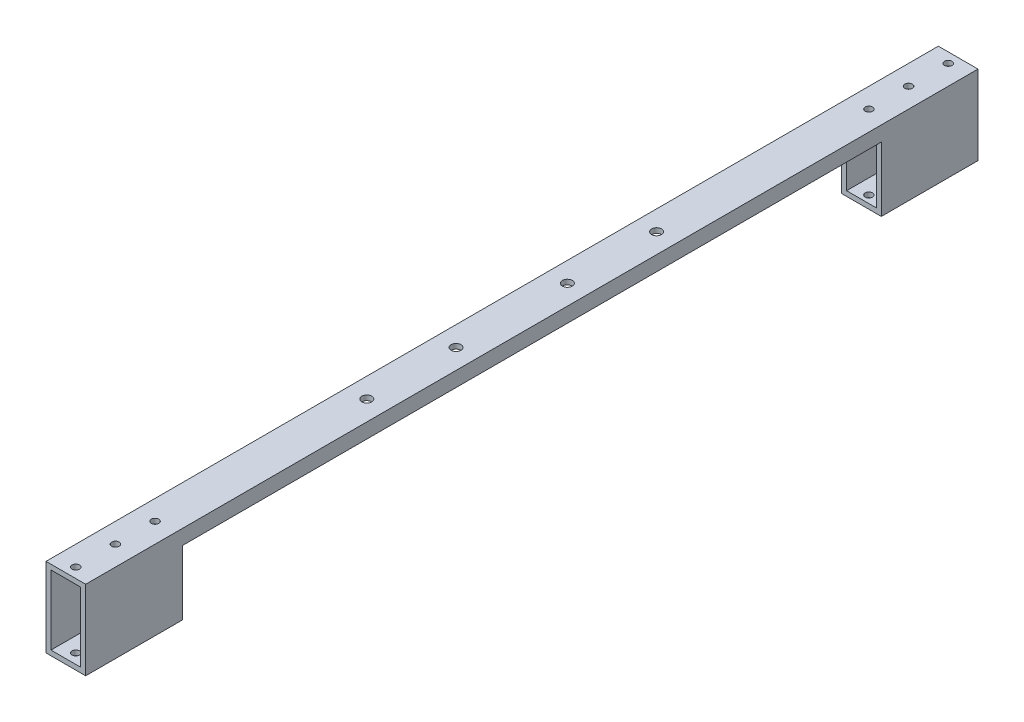
SolidWorks part; units mm, degrees
material "6061-T6 (SS)"
ref_plane "Front Plane" through (0, 0, 0) normal (0, 0, 1) x (1, 0, 0)
ref_plane "Top Plane" through (0, 0, 0) normal (0, 1, 0) x (1, 0, 0)
ref_plane "Right Plane" through (0, 0, 0) normal (1, 0, 0) x (0, 0, -1)
sketch "Sketch1" plane through (0, 0, 0) normal (0, 0, 1) x (1, 0, 0)
  line L1 (-12.7, -25.4) -> (12.7, -25.4)
  line L2 (-12.7, -25.4) -> (-12.7, 25.4)
  line L3 (-12.7, 25.4) -> (12.7, 25.4)
  line L4 (12.7, -25.4) -> (12.7, 25.4)
  line L5 (-12.7, -25.4) -> (12.7, 25.4) construction
  line L6 (-12.7, 25.4) -> (12.7, -25.4) construction
  point P0 (0, 0)
  dimension "D1" = 50.8
  dimension "D2" = 25.4
extrude "Extrude-Thin1" add sketch "Sketch1" along normal blind 571.5 thin thin type one direction reverse wall 3.175
hole_wizard "3/16 (0.1875) Diameter Hole1" positions "3DSketch1" profile "Sketch3" hole size "3/16" standard "ANSI Inch" end condition through all
sketch3d "3DSketch1"
  line L1 (12.7, 25.4, 0) -> (-12.7, 25.4, 0) construction
  line L6 (0, 25.4, 571.5) -> (0, 25.4, 0) construction
  line L7 (12.7, 25.4, 571.5) -> (-12.7, 25.4, 571.5) construction
  point P57 (0, 25.4, 6.35)
  point P59 (0, 25.4, 31.75)
  point P61 (0, 25.4, 57.15)
  point P63 (0, 25.4, 539.75)
  point P65 (0, 25.4, 514.35)
  point P67 (0, 25.4, 565.15)
  dimension "D1" = 25.4
  dimension "D2" = 25.4
  dimension "D3" = 6.35
  dimension "D4" = 25.4
  dimension "D5" = 25.4
  dimension "D6" = 6.35
sketch "Sketch3" plane through (0, 25.4, 565.15) normal (1, 0, 0) x (0, 0, 1)
  line L0 (0, 0) -> (0, 50.8)
  line L1 (0, 50.8) -> (2.3812, 50.8)
  line L2 (2.3812, 50.8) -> (2.3812, 0)
  line L5 (2.3812, 0) -> (0, 0)
  line L11 (0, -6.35) -> (0, 107.95) construction
  dimension "Thru Hole Dia." = 4.7625
  dimension "Thru Hole Depth" = 50.8
hole_wizard "1/4 (0.25) Diameter Hole1" positions "Sketch6" profile "Sketch7" hole size "1/4" standard "ANSI Inch" end condition through all
sketch "Sketch6" plane through (0, 25.4, 0) normal (0, 1, 0) x (1, 0, 0)
  point P0 (0, -321.564)
  point P3 (0, -378.714)
  point P6 (0, -193.167)
  point P9 (0, -250.317)
sketch "Sketch7" plane through (0, 25.4, 321.564) normal (1, 0, 0) x (0, 0, 1)
  line L0 (0, 0) -> (0, 50.8)
  line L1 (0, 50.8) -> (3.175, 50.8)
  line L2 (3.175, 50.8) -> (3.175, 0)
  line L5 (3.175, 0) -> (0, 0)
  line L11 (0, -6.35) -> (0, 107.95) construction
  dimension "Thru Hole Dia." = 6.35
  dimension "Thru Hole Depth" = 50.8
sketch "Sketch10" plane through (12.7, 0, 0) normal (1, 0, 0) x (0, 0, -1)
  line L0 (-509.5748, -25.4) -> (-509.5748, 15.875)
  line L2 (-571.5, -25.4) -> (0, -25.4) construction
  line L3 (-509.5748, 15.875) -> (-61.9252, 15.875)
  line L4 (-61.9252, 15.875) -> (-61.9252, -25.4)
  line L5 (-285.75, -25.4) -> (-285.75, 15.875) construction
  line L6 (-509.5748, -25.4) -> (-61.9252, -25.4)
  dimension "D1" = 447.6496
  dimension "D2" = 41.275
extrude "Cut-Extrude1" cut sketch "Sketch10" against normal through all
